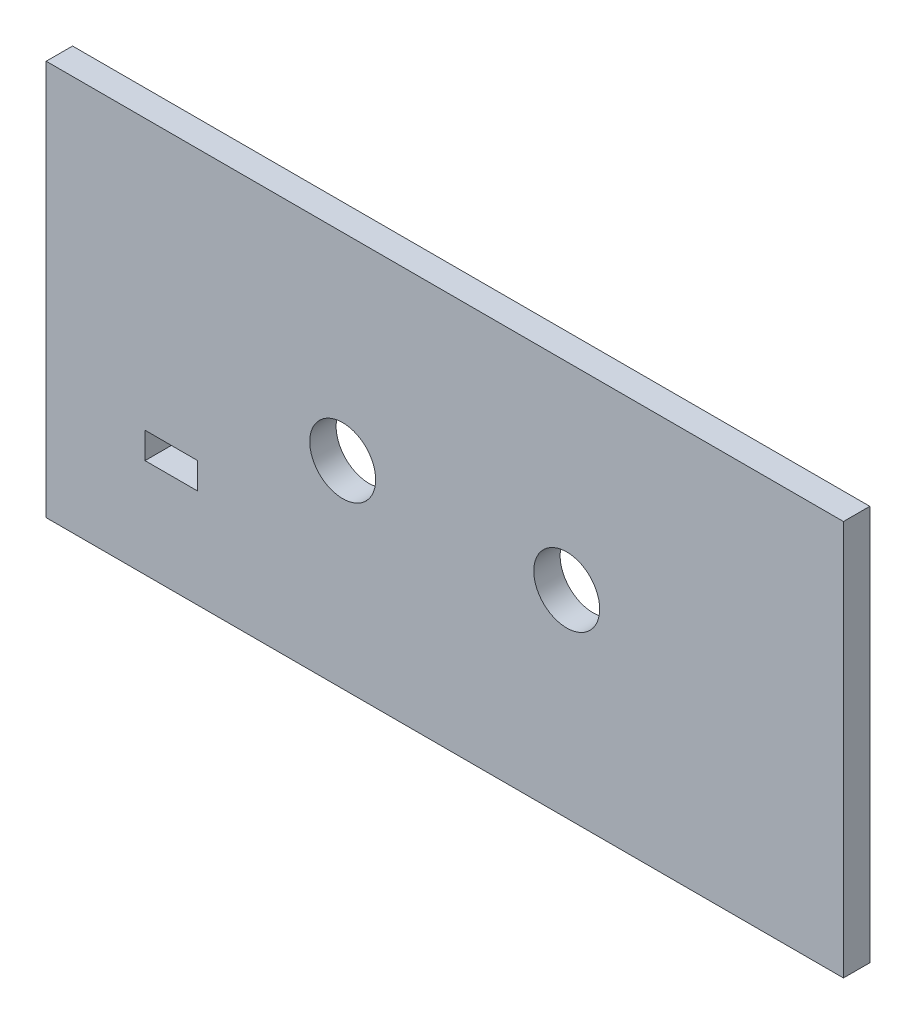
SolidWorks part; units mm, degrees
ref_plane "Front Plane" through (0, 0, 0) normal (0, 0, 1) x (1, 0, 0)
ref_plane "Top Plane" through (0, 0, 0) normal (0, 1, 0) x (1, 0, 0)
ref_plane "Right Plane" through (0, 0, 0) normal (1, 0, 0) x (0, 0, -1)
sketch "Sketch1" plane through (0, 0, 0) normal (0, 0, 1) x (1, 0, 0)
  line L1 (-79, -18.3961) -> (42, -18.3961)
  line L2 (-79, -18.3961) -> (-79, 41.6039)
  line L3 (-79, 41.6039) -> (42, 41.6039)
  line L4 (42, -18.3961) -> (42, 41.6039)
  line L5 (-64, 0.6039) -> (-56, 0.6039)
  line L6 (-64, 0.6039) -> (-64, -3.3961)
  line L7 (-64, -3.3961) -> (-56, -3.3961)
  line L8 (-56, 0.6039) -> (-56, -3.3961)
  circle A2 centre (-34, 11.6039) radius 5
  circle A3 centre (0, 11.6039) radius 5
  point P1 (0, 0)
  point P6 (-79, 11.6039)
  point P7 (42, 11.6039)
  dimension "D3" = 0
  dimension "D4" = 121
  dimension "D5" = 45
  dimension "D6" = 8
  dimension "D7" = 34
  dimension "D10" = 10
  dimension "D2" = 60
  dimension "D8" = 4
  dimension "D9" = 15
  dimension "D11" = 15
extrude "Boss-Extrude1" add sketch "Sketch1" along normal blind 4
